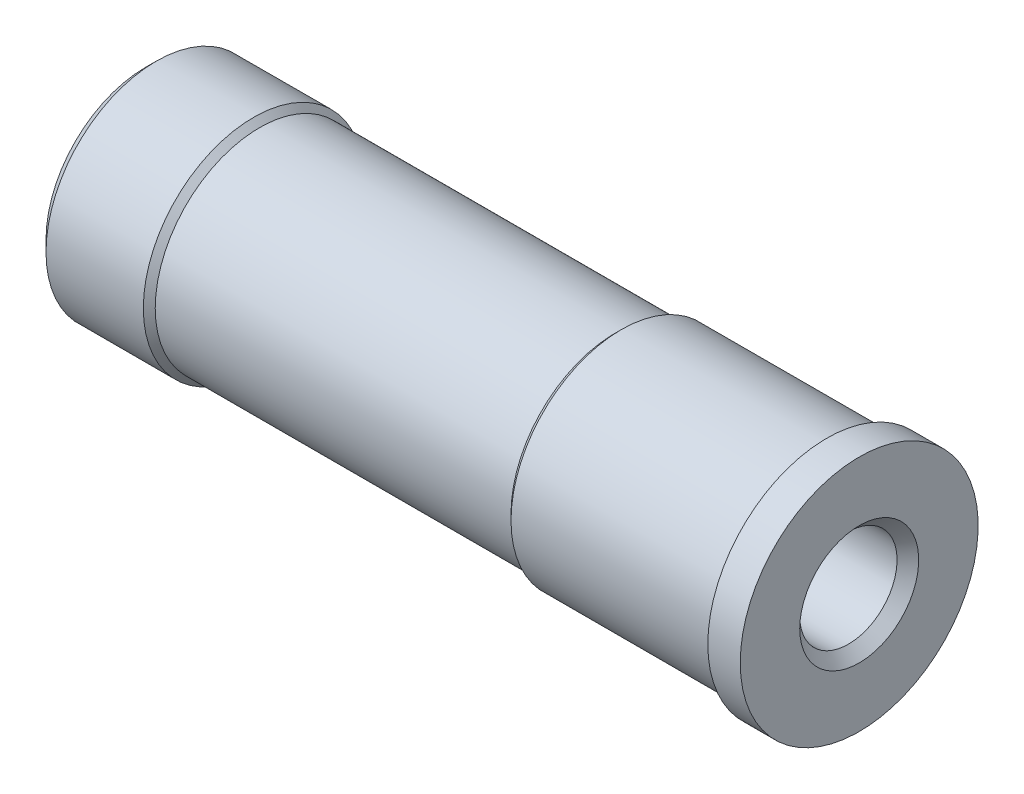
SolidWorks part; units mm, degrees
ref_plane "Płaszczyzna przednia" through (0, 0, 0) normal (0, 0, 1) x (1, 0, 0)
ref_plane "Płaszczyzna górna" through (0, 0, 0) normal (0, 1, 0) x (1, 0, 0)
ref_plane "Płaszczyzna prawa" through (0, 0, 0) normal (1, 0, 0) x (0, 0, -1)
sketch "Szkic1" plane through (0, 0, 0) normal (0, 0, 1) x (1, 0, 0)
  line L0 (0, 4.5) -> (0, 10.2)
  line L1 (0, 10.2) -> (11, 10.2)
  line L2 (11, 10.2) -> (11, 9.65)
  line L3 (11, 9.65) -> (43, 9.65)
  line L4 (43, 9.65) -> (43, 10.2)
  line L5 (43, 10.2) -> (63, 10.2)
  line L6 (63, 10.2) -> (63, 11)
  line L7 (63, 11) -> (66, 11)
  line L8 (66, 11) -> (66, 4.5)
  line L9 (66, 4.5) -> (42, 4.5)
  line L10 (42, 4.5) -> (42, 0)
  line L11 (42, 0) -> (19, 0)
  line L12 (19, 0) -> (19, 4.5)
  line L13 (19, 4.5) -> (0, 4.5)
  line L14 (0, 0) -> (14.9732, 0) construction
  dimension "D1" = 9
  dimension "D2" = 19
  dimension "D3" = 24
  dimension "D4" = 66
  dimension "D5" = 20.4
  dimension "D6" = 19.3
  dimension "D7" = 11
  dimension "D8" = 23
  dimension "D9" = 3
  dimension "D10" = 22
revolve "Obrót1" add sketch "Szkic1" angle 360 about L14
chamfer "Sfazowanie1" distance 1 angle 45 1 edges at (0, 0, 10.2)
chamfer "Sfazowanie2" distance 1 angle 45 2 edges at (11, 0, 10.2) (43, 0, 10.2)
chamfer "Sfazowanie3" distance 1 angle 45 2 edges at (66, 0, 4.5) (0, 0, 4.5)
